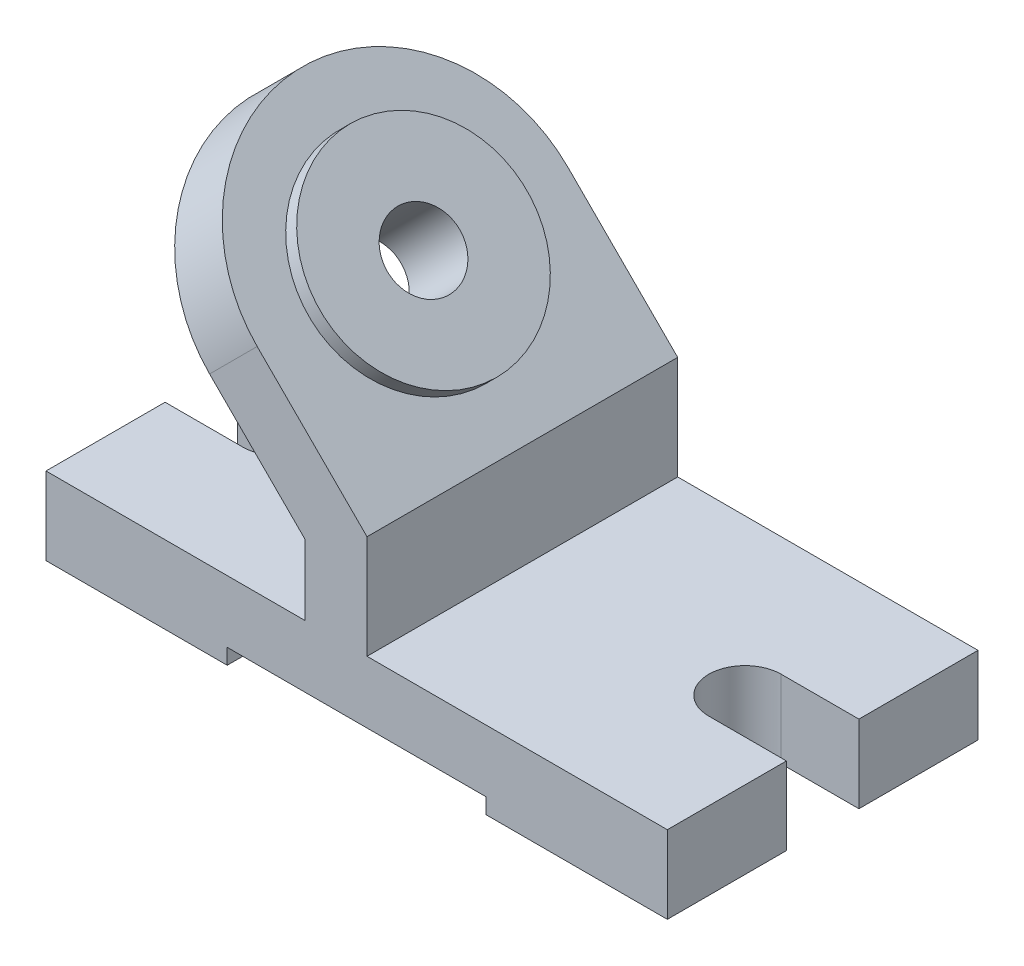
SolidWorks part; units mm, degrees
ref_plane "前视基准面" through (0, 0, 0) normal (0, 0, 1) x (1, 0, 0)
ref_plane "上视基准面" through (0, 0, 0) normal (0, 1, 0) x (1, 0, 0)
ref_plane "右视基准面" through (0, 0, 0) normal (1, 0, 0) x (0, 0, -1)
other "Configuration Table"
sketch "草图1" plane through (0, 0, 0) normal (0, 0, 1) x (1, 0, 0)
  line L0 (-25, 0) -> (-25, -3)
  line L1 (-25, 0) -> (25, 0)
  line L2 (0, 0) -> (0, 12) construction
  line L3 (-60, 12) -> (60, 12)
  line L4 (60, -3) -> (60, 12)
  line L7 (60, -3) -> (25, -3)
  line L8 (25, 0) -> (25, -3)
  line L9 (-60, -3) -> (-25, -3)
  line L11 (-60, -3) -> (-60, 12)
  point P13 (0, 0)
  point P14 (0, 0)
  dimension "D1" = 50
  dimension "D2" = 120
  dimension "D3" = 15
  dimension "D4" = 3
extrude "凸台-拉伸1" add sketch "草图1" along normal mid plane 60
sketch "草图2" plane through (0, 12, 0) normal (0, 1, 0) x (1, 0, 0)
  line L0 (75, 0) -> (45, 0) construction
  line L1 (60, -30) -> (60, 30) construction
  line L2 (75, -7) -> (45, -7)
  line L3 (75, 7) -> (45, 7)
  line L4 (0, 0) -> (0, 38.1127) construction
  line L5 (-75, 0) -> (-45, 0) construction
  line L6 (-75, -7) -> (-45, -7)
  line L7 (-75, 7) -> (-45, 7)
  arc A0 (75, -7) -> (75, 7) centre (75, 0) ccw
  arc A1 (45, 7) -> (45, -7) centre (45, 0) ccw
  arc A2 (-75, -7) -> (-75, 7) centre (-75, 0) cw
  arc A3 (-45, 7) -> (-45, -7) centre (-45, 0) cw
  point P5 (60, 0)
  point P14 (-60, 0)
  dimension "D1" = 7
  dimension "D2" = 90
extrude "切除-拉伸1" cut sketch "草图2" against normal through all
sketch "草图3" plane through (0, 0, 0) normal (0, 0, 1) x (1, 0, 0)
  line L0 (60, 12) -> (-60, 12) construction
  line L1 (-10, 12) -> (2, 12)
  line L2 (-10, 12) -> (-10, 25.6152)
  line L4 (2, 12) -> (2, 32)
  line L6 (2, 32) -> (-19.2132, 53.2132)
  line L7 (-10, 25.6152) -> (-28.4056, 44.0208)
  line L8 (-19.2132, 53.2132) -> (-28.4056, 44.0208)
  line L9 (-60, 12) -> (-60, -3) construction
  point P2 (14.7156, 27)
  point P6 (14.9492, 25.717)
  point P8 (16.0393, 29.4543)
  point P9 (14.9492, 27)
  dimension "D1" = 13
  dimension "D2" = 12
  dimension "D3" = 20
  dimension "D4" = 45
  dimension "D5" = 50
  dimension "D6" = 30
extrude "凸台-拉伸2" add sketch "草图3" along normal mid plane 60
sketch "草图4" plane through (17, 17, 0) normal (0.7071, 0.7071, 0) x (0, 0, -1)
  line L0 (-30, 51.2132) -> (30, 51.2132) construction
  circle A0 centre (0, 51.2132) radius 30
  circle A1 centre (0, 51.2132) radius 20
  circle A2 centre (0, 51.2132) radius 7
  line M2 (30, 51.2132) -> (-30, 51.2132)
  dimension "D1" = 40
  dimension "D2" = 14
extrude "凸台-拉伸3" add sketch "草图4" against normal up to surface (13 mm away) contours A1 A0 M2 | A1 region at (-19.6875, 53.6875, -25) up to face at (-19.2028, 34.818, 0)
extrude "凸台-拉伸4" add sketch "草图4<3>" along normal blind 3 contours A2 A1 M2 | A2 A1 M2 region at (-25.7599, 59.7599, 0) region at (-12.6665, 46.6665, 0)
sketch "草图4<3>" plane through (17, 17, 0) normal (0.7071, 0.7071, 0) x (0, 0, -1) same geometry as "草图4"
sketch "草图5" plane through (17, 17, 0) normal (0.7071, 0.7071, 0) x (0, 0, -1)
  circle A1 centre (0, 51.2132) radius 7
  circle A2 centre (0, 51.2132) radius 7
  dimension "D1" = 0
extrude "切除-拉伸2" cut sketch "草图5" against normal up to next
sketch "草图6" plane through (0, 0, 0) normal (0, 0, 1) x (1, 0, 0)
  line L0 (-20.8658, 36.4811) -> (-35, 12)
  line L1 (-28.4056, 44.0208) -> (-10, 25.6152) construction
  line L2 (-10, 12) -> (-60, 12) construction
  line L3 (-10, 25.6152) -> (-10, 12) construction
  dimension "D1" = 25
  dimension "D2" = 60
rib "筋1" sketch "草图6" sketch "草图6" thickness 10 extrusion direction parallel to sketch draft on no parameters "D1"=10
